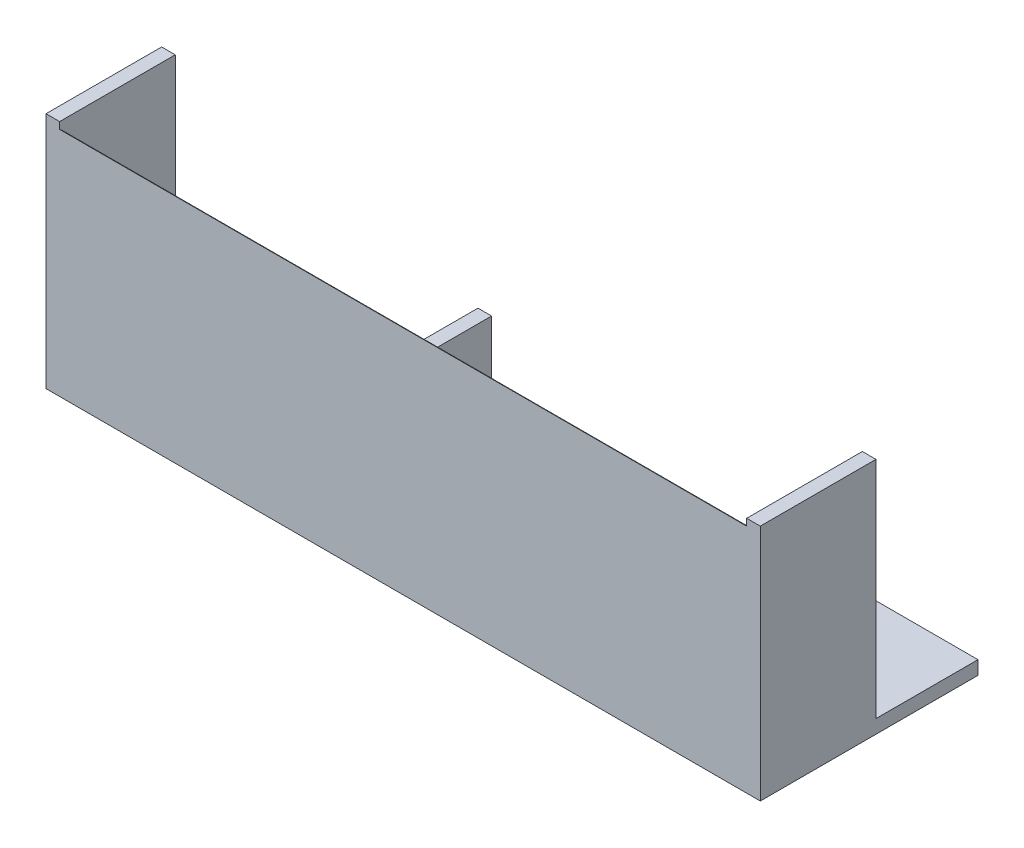
SolidWorks part; units mm, degrees
ref_plane "Front Plane" through (0, 0, 0) normal (0, 0, 1) x (1, 0, 0)
ref_plane "Top Plane" through (0, 0, 0) normal (0, 1, 0) x (1, 0, 0)
ref_plane "Right Plane" through (0, 0, 0) normal (1, 0, 0) x (0, 0, -1)
sketch "Sketch1" plane through (0, 0, 0) normal (0, 0, 1) x (1, 0, 0)
  line L1 (-114.9658, 119.4349) -> (95.0342, 119.4349)
  line L2 (-114.9658, 119.4349) -> (-114.9658, 49.4349)
  line L3 (-114.9658, 49.4349) -> (95.0342, 49.4349)
  line L4 (95.0342, 119.4349) -> (95.0342, 49.4349)
  line L5 (-114.9658, 119.4349) -> (95.0342, 49.4349) construction
  line L6 (-114.9658, 49.4349) -> (95.0342, 119.4349) construction
  point P0 (-9.9658, 84.4349)
  dimension "D1" = 70
  dimension "D2" = 210
extrude "Boss-Extrude1" add sketch "Sketch1" along normal blind 4
sketch "Sketch2" plane through (0, 0, 0) normal (0, 0, 1) x (1, 0, 0)
  line L0 (95.0342, 49.4349) -> (95.0342, 119.4349) construction
  line L1 (-114.9658, 49.4349) -> (95.0342, 49.4349)
  line L2 (-114.9658, 49.4349) -> (-114.9658, 53.4349)
  line L3 (-114.9658, 53.4349) -> (95.0342, 53.4349)
  line L4 (95.0342, 49.4349) -> (95.0342, 53.4349)
  dimension "D1" = 4
extrude "Boss-Extrude2" add sketch "Sketch2" against normal blind 60
sketch "Sketch3" plane through (0, 0, 0) normal (0, 0, 1) x (1, 0, 0)
  line L0 (-9.9658, 9.1029) -> (-9.9658, 130.6974) construction
  line L1 (95.0342, 53.4349) -> (95.0342, 119.4349) construction
  line L2 (95.0342, 53.4349) -> (-114.9658, 53.4349) construction
  line L3 (-114.9658, 119.4349) -> (-110.9658, 119.4349)
  line L4 (-114.9658, 119.4349) -> (-114.9658, 53.4349)
  line L5 (-114.9658, 53.4349) -> (-110.9658, 53.4349)
  line L6 (-110.9658, 119.4349) -> (-110.9658, 53.4349)
  line L8 (95.0342, 119.4349) -> (91.0342, 119.4349)
  line L9 (95.0342, 119.4349) -> (95.0342, 53.4349)
  line L10 (95.0342, 53.4349) -> (91.0342, 53.4349)
  line L11 (91.0342, 119.4349) -> (91.0342, 53.4349)
  dimension "D1" = 4
  dimension "105" = 105
extrude "Boss-Extrude3" add sketch "Sketch3" against normal blind 30
fillet "Fillet1" radius 10 1 edges at (-9.9658, 119.4349, 0)
sketch "Sketch5" plane through (0, 0, 0) normal (0, 0, -1) x (-1, 0, 0)
  line L0 (9.9658, 57.2144) -> (9.9658, 123.7789) construction
  line L1 (-95.0342, 53.4349) -> (-95.0342, 119.4349) construction
  line L2 (-91.0342, 53.4349) -> (110.9658, 53.4349) construction
  line L3 (11.9658, 53.4349) -> (7.9658, 53.4349)
  line L4 (11.9658, 53.4349) -> (11.9658, 109.4349)
  line L5 (11.9658, 109.4349) -> (7.9658, 109.4349)
  line L6 (7.9658, 53.4349) -> (7.9658, 109.4349)
  line L7 (110.9658, 109.4349) -> (-91.0342, 109.4349) construction
  dimension "D1" = 105
  dimension "D2" = 4
  dimension "D3" = 2
extrude "Boss-Extrude4" add sketch "Sketch5" along normal blind 20
